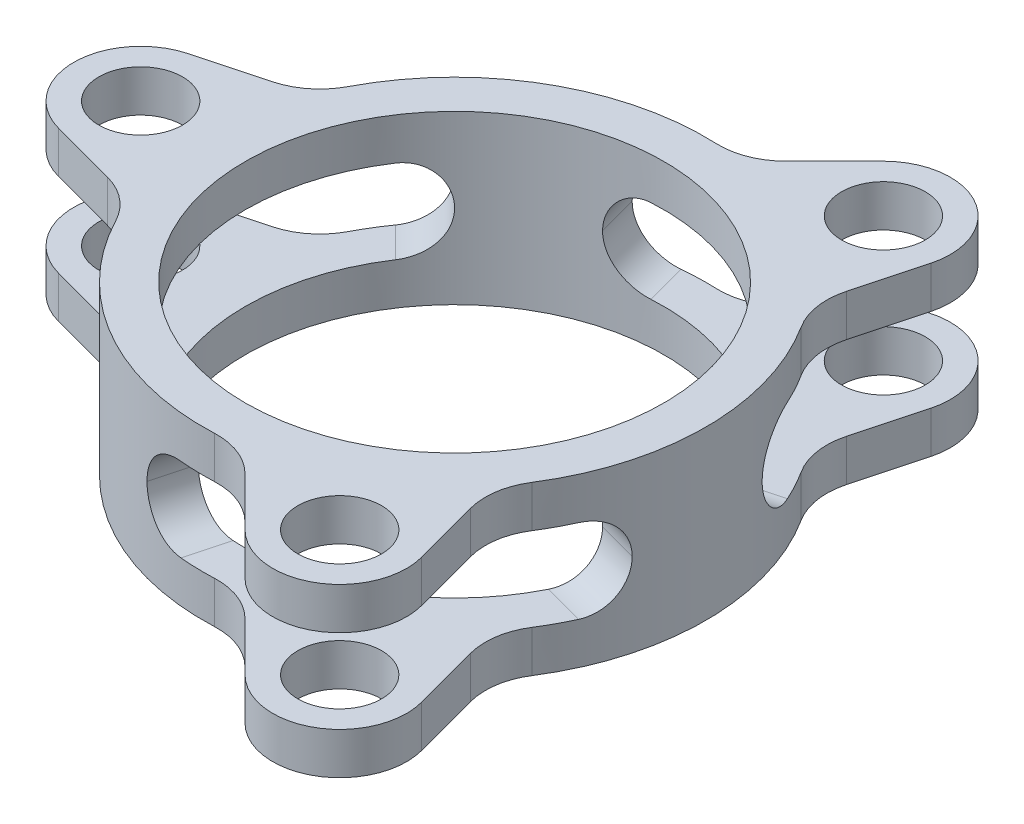
SolidWorks part; units mm, degrees
ref_plane "Front Plane" through (0, 0, 0) normal (0, 0, 1) x (1, 0, 0)
ref_plane "Top Plane" through (0, 0, 0) normal (0, 1, 0) x (1, 0, 0)
ref_plane "Right Plane" through (0, 0, 0) normal (1, 0, 0) x (0, 0, -1)
sketch "Sketch1" plane through (0, 0, 0) normal (0, 1, 0) x (1, 0, 0)
  line L0 (-39.5706, 7.7274) -> (-27.9753, 10.8343)
  line L1 (0, 47.8238) -> (0, 0) construction
  line L2 (0, 0) -> (45.4323, 0) construction
  line L3 (-39.5706, -7.7274) -> (-27.9753, -10.8343)
  line L4 (26.4774, 30.4054) -> (23.3705, 18.8101)
  line L5 (13.0931, 38.1328) -> (4.6048, 29.6445)
  line L6 (13.0931, -38.1328) -> (4.6048, -29.6445)
  line L7 (26.4774, -30.4054) -> (23.3705, -18.8101)
  circle A0 centre (0, 0) radius 37.5 construction
  circle A1 centre (-37.5, 0) radius 5
  circle A2 centre (18.75, 32.476) radius 5
  circle A3 centre (18.75, -32.476) radius 5
  circle A4 centre (-37.5, 0) radius 8
  circle A5 centre (18.75, 32.476) radius 8
  circle A6 centre (18.75, -32.476) radius 8
  circle A7 centre (0, 0) radius 25
  circle A8 centre (0, 0) radius 30
  point P15 (0, 0)
  point P21 (0, 0)
  point P26 (0, 0)
  point P35 (0, 0)
  dimension "D1" = 75
  dimension "D2" = 10
  dimension "D4" = 16
  dimension "D6" = 50
  dimension "D7" = 60
  dimension "D8" = 30
  dimension "D9" = 15
  dimension "D3" = 3
  dimension "D5" = 3
  dimension "D10" = 3
extrude "Boss-Extrude1" add sketch "Sketch1" along normal blind 20 contours A8 A4 A1 | A8 A5 A2 | A8 A6 A3 | A6 A8 A5 A4 A7 | A8 A6 L7 | A8 L6 A6 | A8 L0 A4 | A8 A4 L3 | A8 A5 L5 | A8 L4 A5 | A4 A8 | A5 A8 | A6 A8 region at (-33.7964, 0, -6.838) region at (-31.583, 0, -7.7283) region at (-14.5761, 0, -25.2465) region at (-31.583, 0, 7.7283) region at (-29.7789, 0, 0) region at (9.0986, 0, -31.2159) region at (21.7249, 0, -39.6579) region at (14.8895, 0, -25.7893) region at (9.0986, 0, 31.2159) region at (22.4844, 0, -23.4875) region at (10.9792, 0, 32.6875) region at (14.8895, 0, 25.7893) region at (22.4844, 0, 23.4875)
fillet "Fillet1" radius 8 6 edges at (4.6048, 10, -29.6445) (-27.9753, 10, -10.8343) (-27.9753, 10, 10.8343) (4.6048, 10, 29.6445) (23.3705, 10, -18.8101) (23.3705, 10, 18.8101)
sketch "Sketch8" plane through (0, 0, 0) normal (0, 1, 0) x (1, 0, 0)
  line L0 (0, 0) -> (-50.7007, 50.7007)
  line L1 (0, 0) -> (-50.7007, -50.7007)
  line L2 (-37.5, 0) -> (0, 0) construction
  line L3 (-50.7007, 50.7007) -> (-50.7007, -50.7007)
  dimension "D1" = 45
  dimension "D2" = 45
extrude "Cut-Extrude4" cut sketch "Sketch8" along normal blind 10 from offset 5
fillet "Fillet3" radius 5 4 edges at (-19.4454, 15, -19.4454) (-19.4454, 15, 19.4454) (-19.4454, 5, 19.4454) (-19.4454, 5, -19.4454)
pattern_circular "CirPattern14" count 3 every 120 about axis through (0, 20, 0) along (0, -1, 0) of "Cut-Extrude4", "Fillet3"
